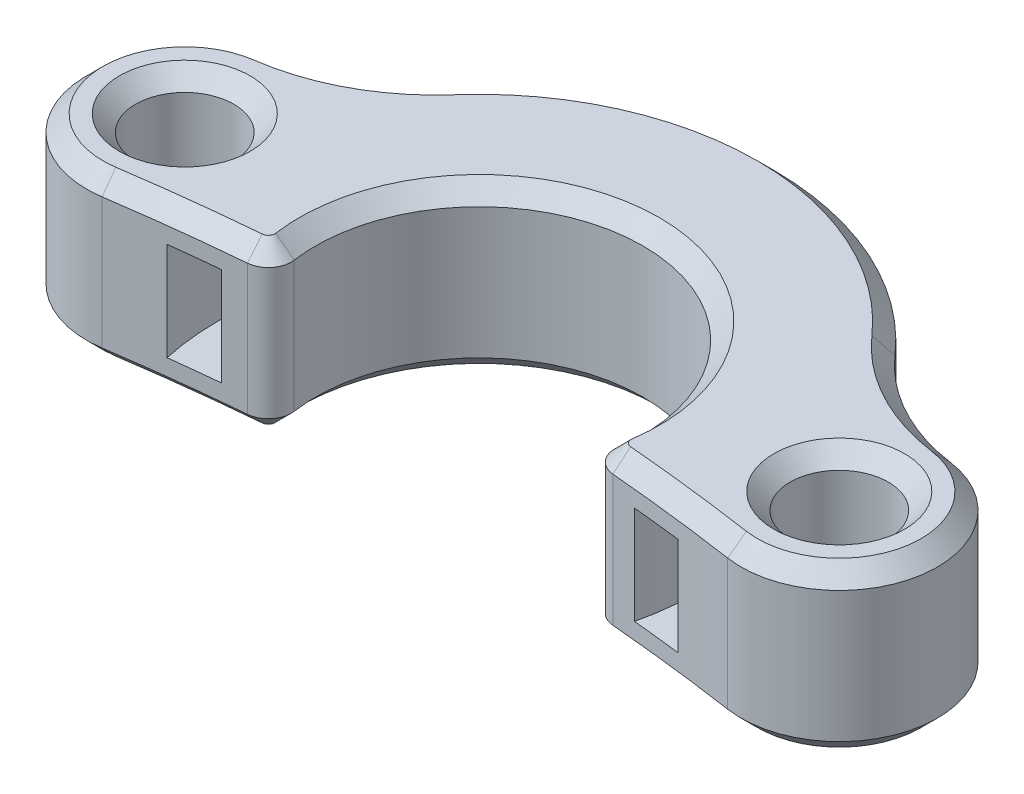
SolidWorks part; units mm, degrees
ref_plane "Front Plane" through (0, 0, 0) normal (0, 0, 1) x (1, 0, 0)
ref_plane "Top Plane" through (0, 0, 0) normal (0, 1, 0) x (1, 0, 0)
ref_plane "Right Plane" through (0, 0, 0) normal (1, 0, 0) x (0, 0, -1)
sketch "Sketch1" plane through (0, 0, 0) normal (0, 1, 0) x (1, 0, 0)
  line L0 (-10, 0) -> (10, 0) construction
  line L1 (0, 0) -> (0, 8) construction
  circle A0 centre (-10, 0) radius 1.5
  circle A1 centre (10, 0) radius 1.5
  circle A2 centre (0, -1) radius 5
  circle A3 centre (-10, 0) radius 3
  circle A4 centre (10, 0) radius 3
  circle A5 centre (0, -1) radius 9
  arc A6 (-10.4196, 2.9705) -> (-6.7553, 4.9469) centre (-11.2588, 8.9115) ccw
  arc A7 (10.4196, 2.9705) -> (6.7553, 4.9469) centre (11.2588, 8.9115) cw
  arc A9 (-9.5588, -2.9674) -> (9.5588, -2.9674) centre (0, -67.2607) cw
  dimension "D1" = 3
  dimension "D3" = 10
  dimension "D2" = 4
  dimension "D5" = 6
  dimension "D7" = 6
  dimension "D8" = 65
  dimension "D4" = 20
  dimension "D6" = 1
extrude "Boss-Extrude1" add sketch "Sketch1" along normal blind 5 contours A5 A3 A0 | A6 A3 A5 | A3 A9 A5 | A5 A9 A2 A4 A3 | A3 A5 A0 | A5 A4 A1 | A4 A7 A5 | A5 A9 A4 | A4 A5 A1 region at (-8.0159, 0, 0.1984) region at (-11.5684, 0, -0.1568) region at (-7.4542, 0, -3.6635) region at (-8.4478, 0, -3.2931) region at (-9.0001, 0, 2.8564) region at (8.4478, 0, -3.2931) region at (9.0001, 0, 2.8564) region at (8.0159, 0, 0.1984) region at (9.3319, 0, -2.8465)
sketch "Sketch2" plane through (0, 0, 0) normal (1, 0, 0) x (0, 0, -1)
  line L0 (4, 5) -> (-2.4373, 5) construction
  line L1 (-2.4373, 5) -> (-2.4373, 0) construction
  line L2 (4, 5) -> (-2.4373, 5) construction
  line L3 (-2.4373, 5) -> (-2.4373, 0) construction
  line L4 (-1, 0) -> (-1, 5) construction
  line L5 (5.5, 1) -> (7, 1)
  line L6 (5.5, 1) -> (5.5, 4)
  line L7 (5.5, 4) -> (7, 4)
  line L8 (7, 1) -> (7, 4)
  line L9 (5.5, 1) -> (7, 4) construction
  line L10 (5.5, 4) -> (7, 1) construction
  point P2 (6.25, 2.5)
  point P8 (-2.4373, 2.5)
  dimension "D1" = 1.5
  dimension "D2" = 1.5
  dimension "D3" = 3
revolve "Cut-Revolve1" cut sketch "Sketch2" angle 360 about L4
fillet "Fillet1" radius 0.7 2 edges at (4.789, 2.5, 2.4373) (-4.789, 2.5, 2.4373)
chamfer "Chamfer1" distance 0.5 angle 45 24 edges at (-10, 0, 1.5) (10, 0, 1.5) (12.969, 0, 0.4304) (8.4105, 0, -3.6307) (0, 0, -8) (-8.4105, 0, -3.6307) (-12.969, 0, 0.4304) (-7.5745, 0, 2.7035) (-5.0951, 0, 2.2391) (0, 0, -4) (5.0951, 0, 2.2391) (7.5745, 0, 2.7035) (-10, 5, 1.5) (10, 5, 1.5) (-5.0951, 5, 2.2391) (-7.5745, 5, 2.7035) (-12.969, 5, 0.4304) (-8.4105, 5, -3.6307) (0, 5, -8) (8.4105, 5, -3.6307) (12.969, 5, 0.4304) (7.5745, 5, 2.7035) (5.0951, 5, 2.2391) (0, 5, -4)
